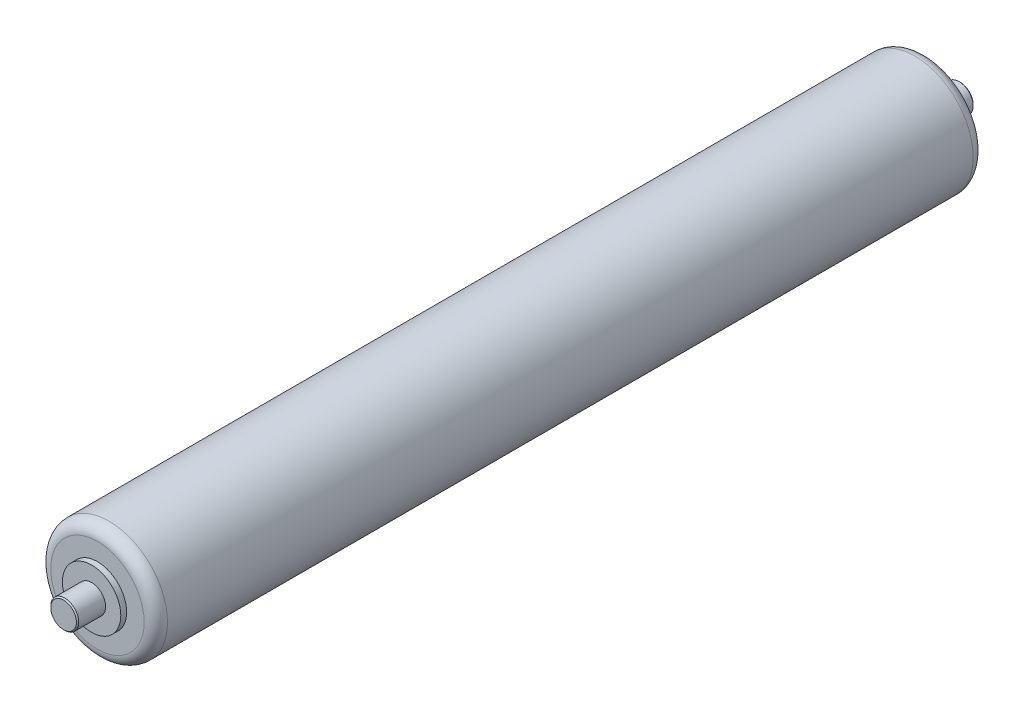
SolidWorks part; units mm, degrees
ref_plane "Front Plane" through (0, 0, 0) normal (0, 0, 1) x (1, 0, 0)
ref_plane "Top Plane" through (0, 0, 0) normal (0, 1, 0) x (1, 0, 0)
ref_plane "Right Plane" through (0, 0, 0) normal (1, 0, 0) x (0, 0, -1)
sketch "Sketch1" plane through (0, 0, 0) normal (0, 1, 0) x (1, 0, 0)
  line L0 (5.5, 14.5) -> (0, 14.5)
  line L1 (0, 14.5) -> (0, -369.5)
  line L2 (0, -369.5) -> (5.5, -369.5)
  line L3 (5.5, -369.5) -> (6, -369)
  line L4 (6, -369) -> (6, -357.5)
  line L5 (6, -357.5) -> (12.5, -357.5)
  line L6 (12.5, -357.5) -> (12.5, -355)
  line L7 (12.5, -355) -> (25, -355)
  line L8 (25, -355) -> (25, 0)
  line L9 (25, 0) -> (12.5, 0)
  line L10 (12.5, 0) -> (12.5, 2.5)
  line L11 (12.5, 2.5) -> (6, 2.5)
  line L12 (6, 2.5) -> (6, 14)
  line L13 (6, 14) -> (5.5, 14.5)
  line L14 (0, 14.5) -> (0, -369.5) construction
revolve "Revolve1" add sketch "Sketch1" angle 360 about L14 reverse direction yes
fillet "Fillet1" radius 5 2 edges at (25, 0, 355) (25, 0, 0)
